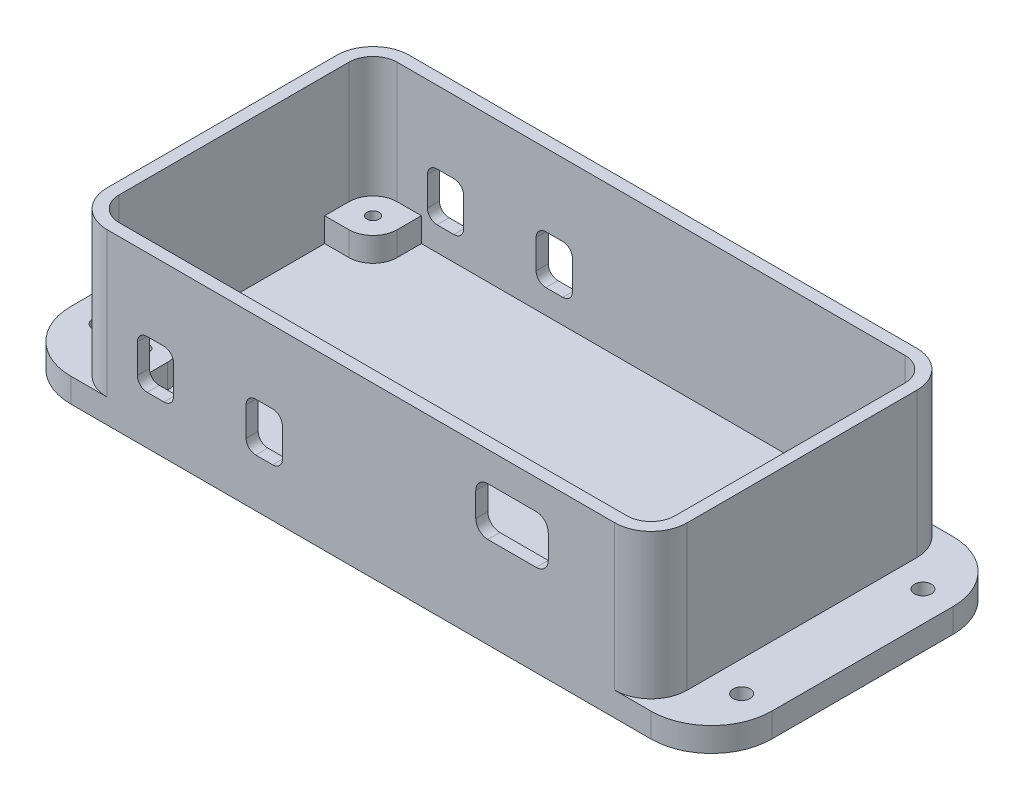
SolidWorks part; units mm, degrees
ref_plane "Front Plane" through (0, 0, 0) normal (0, 0, 1) x (1, 0, 0)
ref_plane "Top Plane" through (0, 0, 0) normal (0, 1, 0) x (1, 0, 0)
ref_plane "Right Plane" through (0, 0, 0) normal (1, 0, 0) x (0, 0, -1)
sketch "Sketch1" plane through (0, 0, 0) normal (0, 1, 0) x (1, 0, 0)
  line L1 (0, 0) -> (147.32, 0)
  line L2 (0, 0) -> (0, 63.5)
  line L3 (0, 63.5) -> (147.32, 63.5)
  line L4 (147.32, 0) -> (147.32, 63.5)
  dimension "D1" = 147.32
  dimension "D2" = 63.5
extrude "Boss-Extrude3" add sketch "Sketch1" along normal blind 5.08
fillet "Fillet4" radius 12.7 4 edges at (147.32, 2.54, -63.5) (147.32, 2.54, 0) (0, 2.54, 0) (0, 2.54, -63.5)
sketch "Sketch4" plane through (0, 5.08, 0) normal (0, 1, 0) x (1, 0, 0)
  line L1 (12.7, 63.5) -> (134.62, 63.5)
  line L2 (12.7, 63.5) -> (12.7, 0)
  line L3 (12.7, 0) -> (134.62, 0)
  line L4 (134.62, 63.5) -> (134.62, 0)
  line L5 (15.24, 60.96) -> (132.08, 60.96)
  line L6 (15.24, 60.96) -> (15.24, 2.54)
  line L7 (15.24, 2.54) -> (132.08, 2.54)
  line L8 (132.08, 60.96) -> (132.08, 2.54)
  dimension "D1" = 2.54
  dimension "D2" = 2.54
  dimension "D3" = 2.54
  dimension "D4" = 2.54
extrude "Boss-Extrude4" add sketch "Sketch4" along normal blind 30.48
sketch "Sketch7" plane through (0, 5.08, 0) normal (0, 1, 0) x (1, 0, 0)
  line L0 (73.66, 60.96) -> (73.66, 2.54) construction
  line L1 (132.08, 60.96) -> (15.24, 60.96) construction
  line L2 (15.24, 2.54) -> (132.08, 2.54) construction
  circle A0 centre (6.35, 50.8) radius 1.778
  circle A1 centre (6.35, 12.7) radius 1.778
  circle A2 centre (140.97, 12.7) radius 1.778
  circle A3 centre (140.97, 50.8) radius 1.778
  dimension "D1" = 6.35
  dimension "D2" = 3.556
  dimension "D3" = 3.556
extrude "Cut-Extrude4" cut sketch "Sketch7" against normal up to next
sketch "Sketch9" plane through (0, 5.08, 0) normal (0, 1, 0) x (1, 0, 0)
  line L0 (73.66, 60.96) -> (73.66, 2.54) construction
  line L1 (15.24, 60.96) -> (25.4, 60.96)
  line L2 (15.24, 60.96) -> (15.24, 50.8)
  line L3 (15.24, 50.8) -> (25.4, 50.8)
  line L4 (25.4, 60.96) -> (25.4, 50.8)
  line L5 (132.08, 60.96) -> (15.24, 60.96) construction
  line L6 (15.24, 2.54) -> (132.08, 2.54) construction
  line L7 (15.24, 31.75) -> (132.08, 31.75) construction
  line L8 (15.24, 60.96) -> (15.24, 2.54) construction
  line L9 (132.08, 2.54) -> (132.08, 60.96) construction
  line L10 (121.92, 60.96) -> (121.92, 50.8)
  line L11 (132.08, 50.8) -> (121.92, 50.8)
  line L12 (132.08, 60.96) -> (132.08, 50.8)
  line L13 (132.08, 60.96) -> (121.92, 60.96)
  line L14 (132.08, 2.54) -> (121.92, 2.54)
  line L15 (132.08, 2.54) -> (132.08, 12.7)
  line L16 (132.08, 12.7) -> (121.92, 12.7)
  line L17 (121.92, 2.54) -> (121.92, 12.7)
  line L18 (25.4, 2.54) -> (25.4, 12.7)
  line L19 (15.24, 12.7) -> (25.4, 12.7)
  line L20 (15.24, 2.54) -> (15.24, 12.7)
  line L21 (15.24, 2.54) -> (25.4, 2.54)
  dimension "D1" = 10.16
  dimension "D2" = 10.16
extrude "Boss-Extrude5" add sketch "Sketch9" along normal blind 5.08
fillet "Fillet9" radius 5.08 4 edges at (121.92, 7.62, -12.7) (25.4, 7.62, -12.7) (121.92, 7.62, -50.8) (25.4, 7.62, -50.8)
sketch "Sketch10" plane through (0, 10.16, 0) normal (0, 1, 0) x (1, 0, 0)
  circle A0 centre (20.32, 55.88) radius 3.175
  circle A1 centre (127, 55.88) radius 3.175
  circle A2 centre (20.32, 7.62) radius 3.175
  circle A3 centre (127, 7.62) radius 3.175
  dimension "D1" = 6.35
  dimension "D2" = 6.35
  dimension "D3" = 6.35
  dimension "D4" = 6.35
extrude "Cut-Extrude7" cut sketch "Sketch10" against normal through all
sketch "Sketch11" plane through (0, 10.16, 0) normal (0, 1, 0) x (1, 0, 0)
  circle A0 centre (20.32, 55.88) radius 3.175
  circle A1 centre (20.32, 55.88) radius 1.27
  circle A2 centre (127, 55.88) radius 3.175
  circle A3 centre (127, 55.88) radius 1.27
  circle A4 centre (20.32, 7.62) radius 3.175
  circle A5 centre (20.32, 7.62) radius 1.27
  circle A6 centre (127, 7.62) radius 3.175
  circle A7 centre (127, 7.62) radius 1.27
  dimension "D1" = 6.35
  dimension "D2" = 2.54
  dimension "D3" = 6.35
  dimension "D4" = 2.54
  dimension "D5" = 6.35
  dimension "D6" = 2.54
  dimension "D7" = 6.35
  dimension "D8" = 2.54
fillet "Fillet11" radius 5.08 4 edges at (132.08, 22.86, -2.54) (15.24, 22.86, -2.54) (132.08, 22.86, -60.96) (15.24, 22.86, -60.96)
fillet "Fillet12" radius 7.62 4 edges at (134.62, 20.32, 0) (134.62, 20.32, -63.5) (12.7, 20.32, -63.5) (12.7, 20.32, 0)
sketch "Sketch12" plane through (0, 0, 0) normal (0, 0, 1) x (1, 0, 0)
  line L0 (105.41, 19.177) -> (105.41, 29.337) construction
  line L1 (97.79, 19.177) -> (113.03, 19.177)
  line L2 (97.79, 19.177) -> (97.79, 29.337)
  line L3 (97.79, 29.337) -> (113.03, 29.337)
  line L4 (113.03, 19.177) -> (113.03, 29.337)
  line L5 (97.79, 24.257) -> (113.03, 24.257) construction
  dimension "D1" = 21.59
  dimension "D2" = 15.24
  dimension "D3" = 10.16
  dimension "D4" = 19.177
extrude "Cut-Extrude8" cut sketch "Sketch12" against normal up to next
fillet "Fillet13" radius 2.54 4 edges at (97.79, 19.177, -1.27) (97.79, 29.337, -1.27) (113.03, 29.337, -1.27) (113.03, 19.177, -1.27)
sketch "Sketch13" plane through (0, 0, 0) normal (0, 0, 1) x (1, 0, 0)
  line L0 (30.48, 20.32) -> (30.48, 10.16) construction
  line L1 (26.67, 20.32) -> (34.29, 20.32)
  line L2 (26.67, 20.32) -> (26.67, 10.16)
  line L3 (26.67, 10.16) -> (34.29, 10.16)
  line L4 (34.29, 20.32) -> (34.29, 10.16)
  line L5 (49.53, 20.32) -> (57.15, 20.32)
  line L6 (49.53, 20.32) -> (49.53, 10.16)
  line L7 (49.53, 10.16) -> (57.15, 10.16)
  line L8 (57.15, 20.32) -> (57.15, 10.16)
  line L9 (53.34, 20.32) -> (53.34, 10.16) construction
  dimension "D1" = 5.08
  dimension "D2" = 10.16
  dimension "D3" = 10.16
  dimension "D4" = 33.02
  dimension "D5" = 7.62
  dimension "D6" = 7.62
extrude "Cut-Extrude9" cut sketch "Sketch13" against normal through all
fillet "Fillet14" radius 2.032 16 edges at (34.29, 10.16, -62.23) (57.15, 10.16, -62.23) (34.29, 20.32, -62.23) (57.15, 20.32, -62.23) (26.67, 20.32, -62.23) (49.53, 20.32, -62.23) (49.53, 10.16, -62.23) (26.67, 10.16, -62.23) (49.53, 10.16, -1.27) (26.67, 10.16, -1.27) (49.53, 20.32, -1.27) (26.67, 20.32, -1.27) (57.15, 20.32, -1.27) (34.29, 20.32, -1.27) (57.15, 10.16, -1.27) (34.29, 10.16, -1.27)
extrude "Boss-Extrude7" add sketch "Sketch11" against normal blind 5.08
